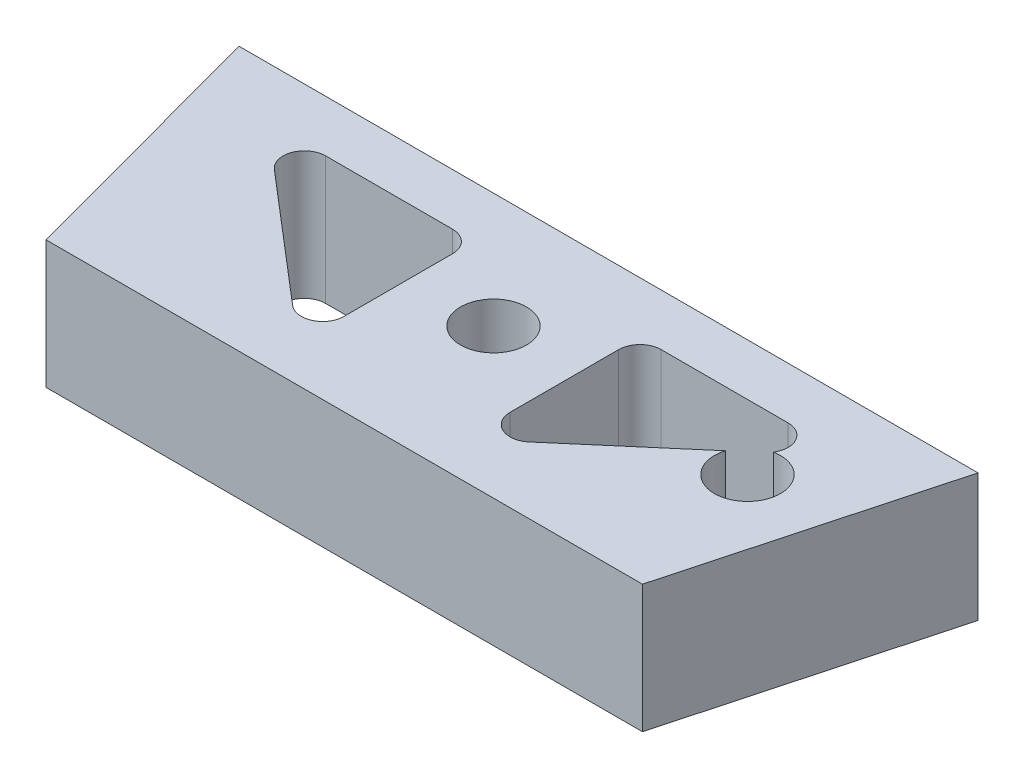
SolidWorks part; units mm, degrees
ref_plane "前视基准面" through (0, 0, 0) normal (0, 0, 1) x (1, 0, 0)
ref_plane "上视基准面" through (0, 0, 0) normal (0, 1, 0) x (1, 0, 0)
ref_plane "右视基准面" through (0, 0, 0) normal (1, 0, 0) x (0, 0, -1)
sketch "草图1" plane through (0, 0, 0) normal (0, 1, 0) x (1, 0, 0)
  line L0 (-0.8626, -12.8028) -> (12.835, -12.8028)
  line L1 (12.835, -12.8028) -> (16.186, -0.4028)
  line L2 (-15.165, -12.8028) -> (-18.5019, -0.4028)
  line L3 (-5.0559, -8.9245) -> (-5.0559, -3.8274)
  line L4 (-6.0559, -2.8274) -> (-12.0109, -2.8274)
  line L5 (-12.6612, -4.5871) -> (-6.7061, -9.6842)
  line L6 (-1.1579, 1.9171) -> (-1.1579, -9.2961) construction
  line L7 (10.3454, -4.5871) -> (4.3903, -9.6842)
  line L8 (3.7401, -2.8274) -> (9.6951, -2.8274)
  line L9 (2.7401, -8.9245) -> (2.7401, -3.8274)
  line L25 (-15.165, -12.8028) -> (-0.8626, -12.8028)
  line L40 (-18.5019, -0.4028) -> (16.186, -0.4028)
  arc A0 (4.3903, -9.6842) -> (2.7401, -8.9245) centre (3.7401, -8.9245) cw
  arc A1 (10.3454, -4.5871) -> (9.6951, -2.8274) centre (9.6951, -3.8274) ccw
  arc A2 (3.7401, -2.8274) -> (2.7401, -3.8274) centre (3.7401, -3.8274) ccw
  arc A3 (-5.0559, -8.9245) -> (-6.7061, -9.6842) centre (-6.0559, -8.9245) cw
  arc A4 (-5.0559, -3.8274) -> (-6.0559, -2.8274) centre (-6.0559, -3.8274) ccw
  arc A5 (-12.0109, -2.8274) -> (-12.6612, -4.5871) centre (-12.0109, -3.8274) ccw
  point P14 (2.7401, -11.0968)
  point P17 (12.4013, -2.8274)
  point P20 (2.7401, -2.8274)
  point P23 (-5.0559, -11.0968)
  point P26 (-5.0559, -2.8274)
  point P29 (-14.7171, -2.8274)
  point P31 (-1.1579, -0.4028)
  dimension "D1" = 1
extrude "凸台-拉伸1" add sketch "草图1" against normal blind 1 contours L40 L2 L25 L0 L1 A5 L4 A4 L3 A3 L5 A2 L8 A1 L7 A0 L9 region at (-1.1622, 0, 6.5764)
extrude "凸台-拉伸2" add sketch "草图1<8>" along normal blind 5
sketch "草图1<8>" plane through (0, 0, 0) normal (0, 1, 0) x (1, 0, 0) same geometry as "草图1"
sketch "草图2" plane through (0, 5, 0) normal (0, 1, 0) x (1, 0, 0)
  line L0 (-15.165, -12.8028) -> (12.835, -12.8028) construction
  circle A0 centre (-1.1579, -5.8028) radius 1.55
  dimension "D1" = 7
extrude "切除-拉伸1" cut sketch "草图2" against normal up to next
sketch "草图3" plane through (0, 5, 0) normal (0, 1, 0) x (1, 0, 0)
  circle A0 centre (10.8421, -5.8823) radius 1.55
extrude "切除-拉伸2" cut sketch "草图3" against normal up to surface (6 mm away) up to face at (-1.1579, -1, 7.3528)
